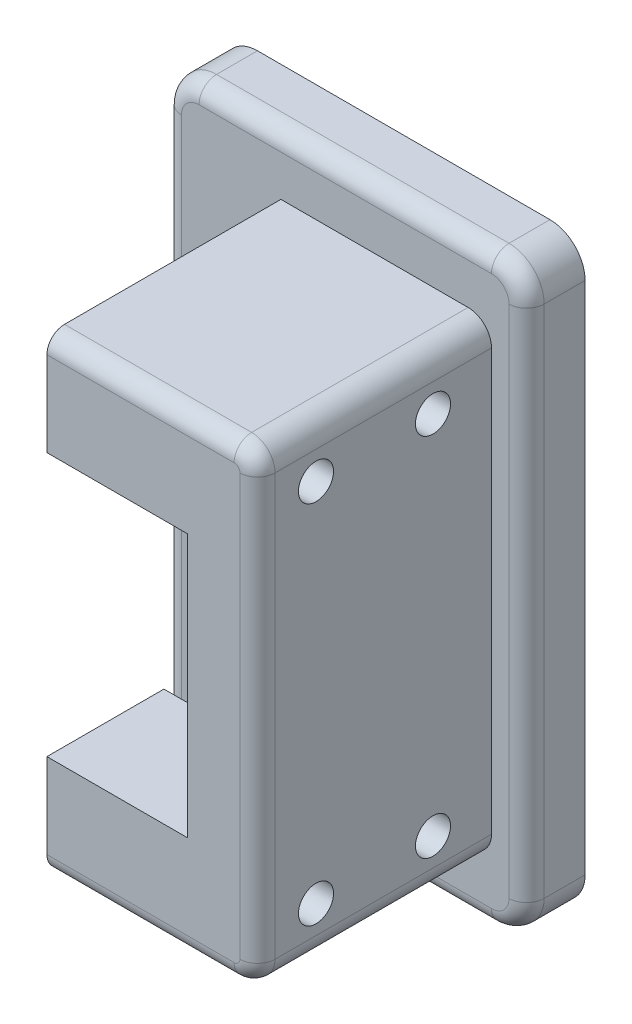
SolidWorks part; units mm, degrees
ref_plane "Front Plane" through (0, 0, 0) normal (0, 0, 1) x (1, 0, 0)
ref_plane "Top Plane" through (0, 0, 0) normal (0, 1, 0) x (1, 0, 0)
ref_plane "Right Plane" through (0, 0, 0) normal (1, 0, 0) x (0, 0, -1)
sketch "Sketch1" plane through (0, 0, 0) normal (0, 0, 1) x (1, 0, 0)
  line L0 (-130, -28) -> (-148, -28)
  line L1 (-148, -28) -> (-148, -36.75)
  line L2 (-148, -68) -> (-130, -68)
  line L3 (-148, -59.25) -> (-148, -68)
  line L4 (-148, -36.75) -> (-136, -36.75)
  line L6 (-148, -59.25) -> (-136, -59.25)
  line L7 (-136, -36.75) -> (-136, -59.25)
  line L8 (-130, -28) -> (-130, -68)
  dimension "D1" = 40
  dimension "D2" = 6
  dimension "D3" = 22.5
  dimension "D4" = 8.75
  dimension "D5" = 12
extrude "Boss-Extrude1" add sketch "Sketch1" against normal blind 20
sketch "Sketch2" plane through (0, 0, 0) normal (0, 0, 1) x (1, 0, 0)
  line L7 (-130, -28) -> (-148, -28)
  line L8 (-130, -28) -> (-148, -28)
  line L9 (-148, -28) -> (-148, -36.75)
  line L10 (-148, -28) -> (-148, -36.75)
  line L11 (-148, -36.75) -> (-136, -36.75)
  line L12 (-148, -36.75) -> (-136, -36.75)
  line L13 (-136, -36.75) -> (-136, -59.25)
  line L14 (-136, -36.75) -> (-136, -59.25)
  line L15 (-136, -59.25) -> (-148, -59.25)
  line L16 (-136, -59.25) -> (-148, -59.25)
  line L17 (-148, -59.25) -> (-148, -68)
  line L18 (-148, -59.25) -> (-148, -68)
  line L19 (-148, -68) -> (-130, -68)
  line L20 (-148, -68) -> (-130, -68)
  line L22 (-130, -68) -> (-130, -28)
  line L23 (-130, -68) -> (-130, -28)
  dimension "D1" = 0
sketch "Sketch3" plane through (0, 0, -20) normal (0, 0, -1) x (-1, 0, 0)
  line L0 (148, -68) -> (130, -68) construction
  line L1 (155, -73) -> (130, -73)
  line L2 (158, -70) -> (158, -26)
  line L3 (155, -23) -> (130, -23)
  line L4 (127, -70) -> (127, -26)
  line L5 (130, -28) -> (148, -28) construction
  line L6 (148, -28) -> (148, -36.75) construction
  line L7 (130, -68) -> (130, -28) construction
  arc A0 (155, -73) -> (158, -70) centre (155, -70) ccw
  arc A1 (130, -73) -> (127, -70) centre (130, -70) cw
  arc A2 (130, -23) -> (127, -26) centre (130, -26) ccw
  arc A3 (158, -26) -> (155, -23) centre (155, -26) ccw
  dimension "D5" = 3
  dimension "D1" = 5
  dimension "D2" = 5
  dimension "D3" = 10
  dimension "D4" = 3
extrude "Boss-Extrude2" add sketch "Sketch3" along normal blind 5
fillet "Fillet1" radius 2 2 edges at (-130, -28, -10) (-130, -68, -10)
sketch "Sketch4" plane through (0, -68, 0) normal (0, -1, 0) x (1, 0, 0)
  line L1 (-148, -20) -> (-138, -20)
  line L2 (-148, -20) -> (-148, -10)
  line L3 (-148, -10) -> (-138, -10)
  line L4 (-138, -20) -> (-138, -10)
  dimension "D1" = 10
  dimension "D2" = 10
extrude "Cut-Extrude1" cut sketch "Sketch4" against normal up to surface (8.75 mm away) up to face at (-142, -59.25, -10)
sketch "Sketch5" plane through (-148, 0, 0) normal (-1, 0, 0) x (0, 0, 1)
  line L2 (-20, -48) -> (0, -48) construction
  line L3 (-20, -70) -> (-20, -26) construction
  line L4 (0, -36.75) -> (0, -59.25) construction
  circle A0 centre (-5, -32.375) radius 1.5
  circle A1 centre (-15, -32.375) radius 1.5
  circle A2 centre (-15, -63.625) radius 1.5
  circle A3 centre (-5, -63.625) radius 1.5
extrude "Cut-Extrude2" cut sketch "Sketch5" against normal through all
fillet "Fillet2" radius 1.5 13 edges at (-140, -68, 0) (-130.5858, -67.4142, 0) (-130, -48, 0) (-140, -28, 0) (-157.1213, -23.8787, -20) (-158, -48, -20) (-157.1213, -72.1213, -20) (-142.5, -73, -20) (-127.8787, -72.1213, -20) (-127, -48, -20) (-127.8787, -23.8787, -20) (-130.5858, -28.5858, 0) (-142.5, -23, -20)
